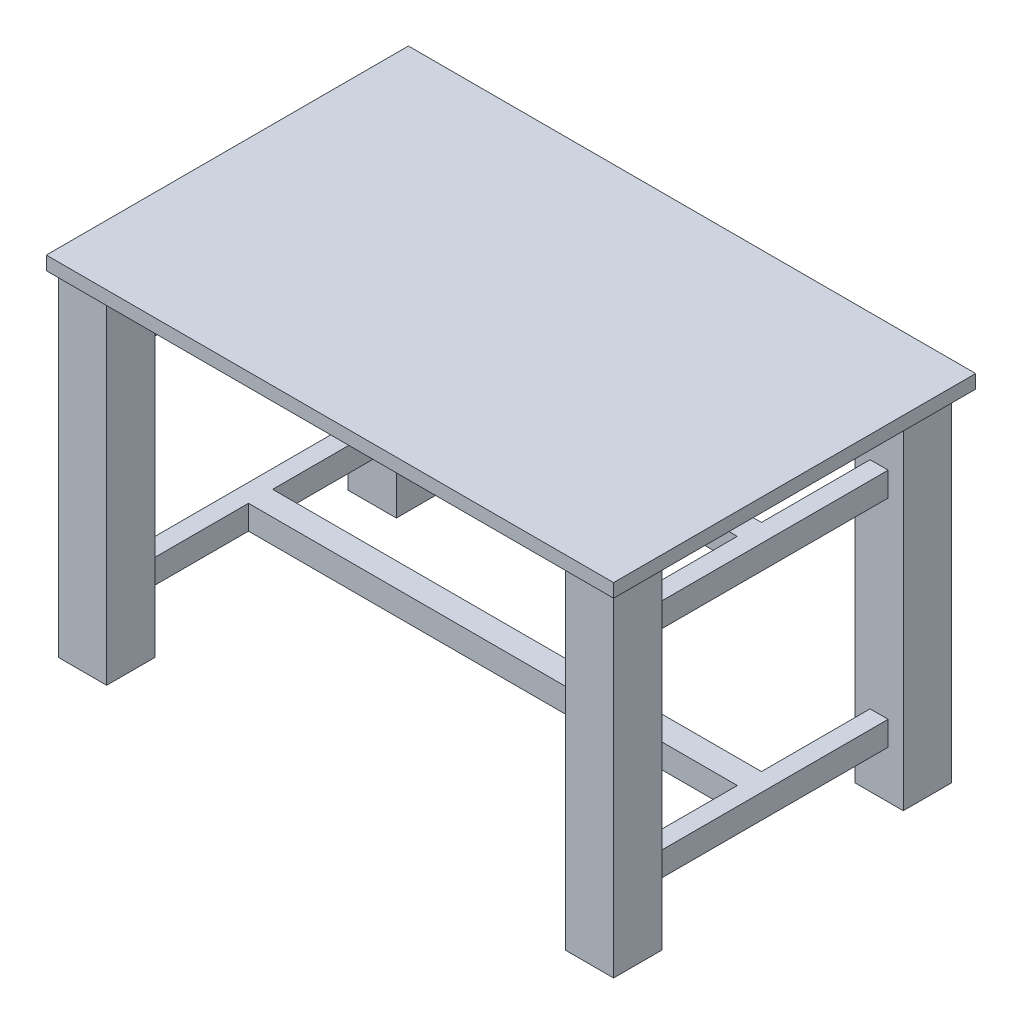
SolidWorks part; units mm, degrees
material "Alloy Steel"
ref_plane "Front Plane" through (0, 0, 0) normal (0, 0, 1) x (1, 0, 0)
ref_plane "Top Plane" through (0, 0, 0) normal (0, 1, 0) x (1, 0, 0)
ref_plane "Right Plane" through (0, 0, 0) normal (1, 0, 0) x (0, 0, -1)
sketch "Sketch1" plane through (0, 0, 0) normal (0, 1, 0) x (1, 0, 0)
  line L0 (-366.1707, 0) -> (17942.3634, 0) construction
  line L1 (0, -366.1707) -> (0, 17942.3634) construction
  line L2 (-584.2, 254) -> (-482.6, 254)
  line L3 (-584.2, -355.6) -> (584.2, -355.6)
  line L4 (-584.2, -355.6) -> (-584.2, 355.6)
  line L5 (-584.2, 355.6) -> (584.2, 355.6)
  line L6 (584.2, -355.6) -> (584.2, 355.6)
  line L7 (0, 355.6) -> (0, -355.6) construction
  line L8 (-584.2, 0) -> (584.2, 0) construction
  line L9 (-482.6, 254) -> (-482.6, 355.6)
  line L10 (482.6, 254) -> (482.6, 355.6)
  line L11 (584.2, 254) -> (482.6, 254)
  line L12 (584.2, -254) -> (482.6, -254)
  line L13 (482.6, -254) -> (482.6, -355.6)
  line L14 (-482.6, -254) -> (-482.6, -355.6)
  line L15 (-584.2, -254) -> (-482.6, -254)
  line L16 (-533.4, 254) -> (-533.4, -254) construction
  line L17 (-552.45, 254) -> (-552.45, -254)
  line L18 (-514.35, 254) -> (-514.35, -254)
  line L19 (514.35, 254) -> (514.35, -254)
  line L20 (552.45, 254) -> (552.45, -254)
  line L21 (-514.35, 25.4) -> (514.35, 25.4)
  line L22 (-514.35, -25.4) -> (514.35, -25.4)
  point P4 (0, 0)
  dimension "D1" = 1168.4
  dimension "D2" = 711.2
  dimension "D3" = 101.6
  dimension "D4" = 38.1
  dimension "D5" = 50.8
extrude "Boss-Extrude1" add sketch "Sketch1" against normal blind 704.85 contours L2 L9 L5 L4 | L11 L6 L5 L10 | L12 L13 L3 L6 | L15 L4 L3 L14 | L18 L2 L17 L15 | L18 L22 L19 L21 | L20 L11 L19 L12 region at (-533.4, 0, -304.8) region at (-533.4, 0, 0) region at (-533.4, 0, 304.8) region at (0, 0, 0) region at (533.4, 0, -304.8) region at (533.4, 0, 0) region at (533.4, 0, 304.8)
sketch "Sketch2" plane through (0, 0, 0) normal (1, 0, 0) x (0, 0, -1)
  line L0 (254, -704.85) -> (254, 0) construction
  line L1 (-254, 0) -> (254, 0)
  line L2 (-254, 0) -> (-254, -100)
  line L3 (-254, -100) -> (254, -100)
  line L4 (254, 0) -> (254, -100)
  line L5 (-254, -704.85) -> (-254, 0) construction
  line L6 (-254, -150.8) -> (254, -150.8)
  line L7 (-254, -150.8) -> (-254, -554.05)
  line L8 (-254, -554.05) -> (254, -554.05)
  line L9 (254, -150.8) -> (254, -554.05)
  line L10 (254, -704.85) -> (254, 0) construction
  line L11 (-254, -704.85) -> (254, -704.85)
  line L12 (-254, -704.85) -> (-254, -604.85)
  line L13 (-254, -604.85) -> (254, -604.85)
  line L14 (254, -704.85) -> (254, -604.85)
  dimension "D1" = 100
  dimension "D2" = 50.8
  dimension "D3" = 50.8
extrude "Cut-Extrude1" cut sketch "Sketch2" against normal through all both and the other way through all
sketch "Sketch3" plane through (0, 0, 0) normal (0, 1, 0) x (1, 0, 0)
  line L0 (-584.2, -355.6) -> (-482.6, -355.6) construction
  line L1 (-596.9, 393.7) -> (596.9, 393.7)
  line L2 (-596.9, 393.7) -> (-596.9, -368.3)
  line L3 (-596.9, -368.3) -> (596.9, -368.3)
  line L4 (596.9, 393.7) -> (596.9, -368.3)
  line L5 (0, -368.3) -> (0, 393.7) construction
  line L6 (-596.9, 12.7) -> (596.9, 12.7) construction
  point P0 (0, 12.7)
  point P4 (0, 14.3663)
  dimension "D1" = 762
  dimension "D2" = 1193.8
  dimension "D3" = 12.7
extrude "Boss-Extrude2" add sketch "Sketch3" along normal blind 28.5 separate body
